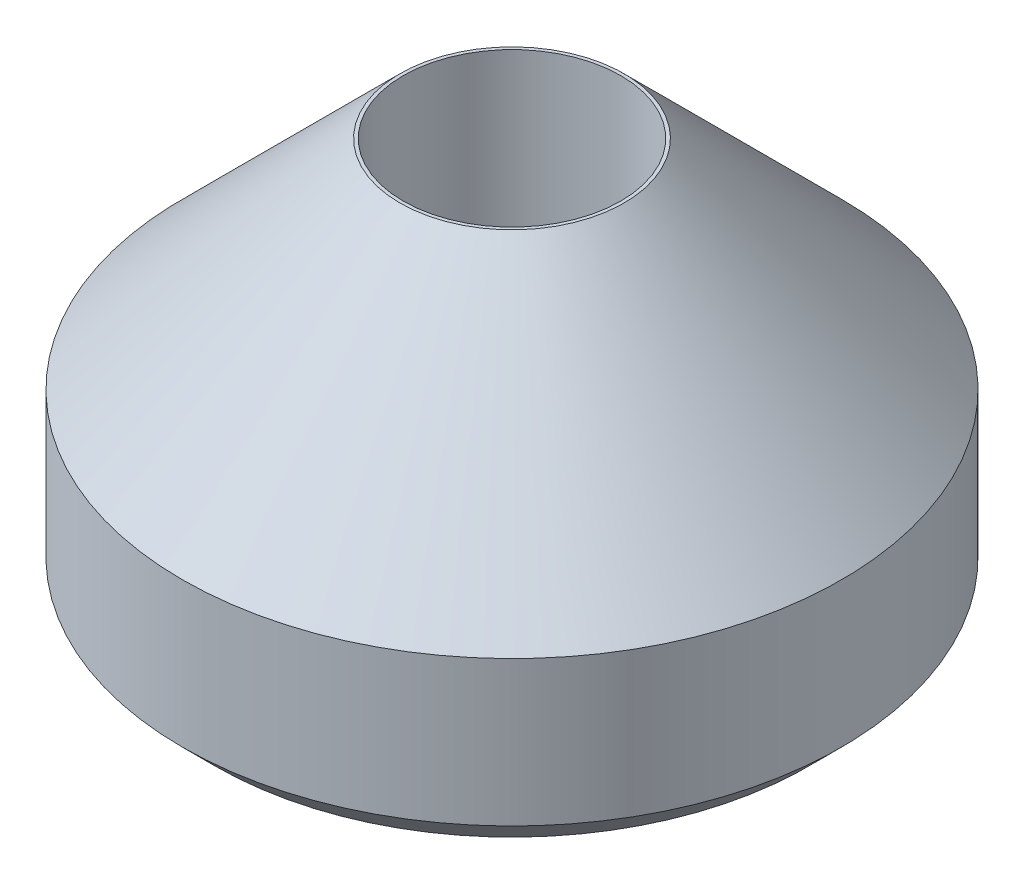
SolidWorks part; units mm, degrees
ref_plane "Front Plane" through (0, 0, 0) normal (0, 0, 1) x (1, 0, 0)
ref_plane "Top Plane" through (0, 0, 0) normal (0, 1, 0) x (1, 0, 0)
ref_plane "Right Plane" through (0, 0, 0) normal (1, 0, 0) x (0, 0, -1)
sketch "Sketch1" plane through (0, 0, 0) normal (0, 1, 0) x (1, 0, 0)
  circle A0 centre (0, 0) radius 5
  dimension "D1" = 10
extrude "Boss-Extrude1" add sketch "Sketch1" along normal blind 1
sketch "Sketch2" plane through (0, 1, 0) normal (0, 1, 0) x (1, 0, 0)
  circle A0 centre (0, 0) radius 5
  dimension "D1" = 10
extrude "Boss-Extrude2" add sketch "Sketch2" along normal blind 5
sketch "Sketch3" plane through (0, 6, 0) normal (0, 1, 0) x (1, 0, 0)
  circle A1 centre (0, 0) radius 1.65
  dimension "D1" = 3.3
extrude "Cut-Extrude3" cut sketch "Sketch3" against normal blind 3 contours A1
chamfer "Chamfer3" distance 3.3 angle 45 1 edges at (0, 6, 5)
chamfer "Chamfer4" distance 0.5 angle 45 1 edges at (0, 0, 5)
sketch "Sketch4" plane through (0, 0, 0) normal (0, -1, 0) x (1, 0, 0)
  line L0 (0, 0) -> (1.4339, -2.0479) construction
  line L1 (0, 0) -> (-1.4339, -2.0479) construction
  line L2 (0, 0) -> (0, -4.5) construction
  line L3 (-2.0075, -2.867) -> (-1.4339, -2.0479)
  line L4 (2.0075, -2.867) -> (1.4339, -2.0479)
  line L5 (-0.5, 0) -> (0.5, 0)
  line L6 (0.5, 0) -> (0.5, -3.5)
  line L7 (0.5, -3.5) -> (-0.5, -3.5)
  line L8 (-0.5, -3.5) -> (-0.5, 0)
  arc A0 (1.4339, -2.0479) -> (-1.4339, -2.0479) centre (0, 0) ccw
  arc A1 (2.0075, -2.867) -> (-2.0075, -2.867) centre (0, 0) ccw
  circle A2 centre (0, 0) radius 4.5 construction
  dimension "D1" = 5
  dimension "D2" = 7
  dimension "D5" = 1
  dimension "D6" = 3.5
  dimension "D3" = 70
  dimension "D4" = 35
extrude "Cut-Extrude4" cut sketch "Sketch4" against normal blind 1
fillet "Fillet1" radius 0.5 8 edges at (1.4339, 0.5, -2.0479) (2.0075, 0.5, -2.867) (0.5, 0.5, -3.5) (0.5, 0.5, 0) (-0.5, 0.5, 0) (-0.5, 0.5, -3.5) (-1.4339, 0.5, -2.0479) (-2.0075, 0.5, -2.867)
equation "\"DIAM\"= 10"
equation "\"D1@Sketch1\"=\"DIAM\""
equation "\"D1@Sketch4\"=\"DIAM\"-5"
equation "\"D2@Sketch4\"=\"DIAM\"-3"
equation "\"D6@Sketch4\"=\"DIAM\"/2-1.5"
equation "\"ANGLE\"= 70"
equation "\"D3@Sketch4\"=\"ANGLE\""
equation "\"D4@Sketch4\"=\"ANGLE\"/2"
